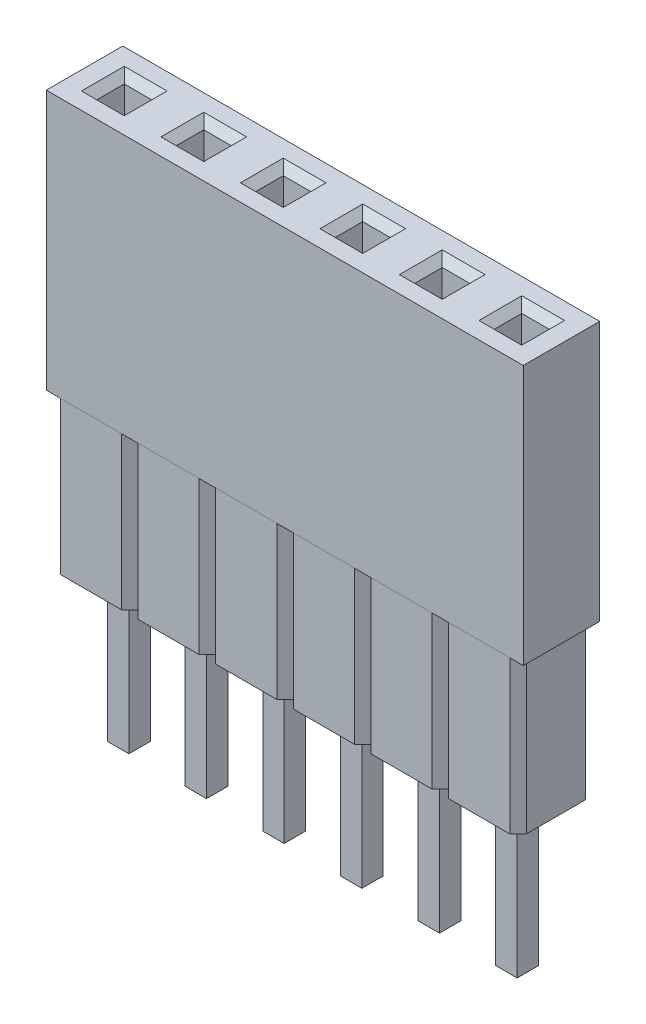
SolidWorks part; units mm, degrees
ref_plane "Alzado" through (0, 0, 0) normal (0, 0, 1) x (1, 0, 0)
ref_plane "Planta" through (0, 0, 0) normal (0, 1, 0) x (1, 0, 0)
ref_plane "Vista lateral" through (0, 0, 0) normal (1, 0, 0) x (0, 0, -1)
sketch "Croquis1" plane through (0, 0, 0) normal (0, 1, 0) x (1, 0, 0)
  line L1 (-7.8, 1.25) -> (7.8, 1.25)
  line L2 (-7.8, 1.25) -> (-7.8, -1.25)
  line L3 (-7.8, -1.25) -> (7.8, -1.25)
  line L4 (7.8, 1.25) -> (7.8, -1.25)
  line L5 (-7.8, 1.25) -> (7.8, -1.25) construction
  line L6 (-7.8, -1.25) -> (7.8, 1.25) construction
  point P0 (0, 0)
  dimension "D1" = 2.5
  dimension "D2" = 15.6
extrude "Saliente-Extruir1" add sketch "Croquis1" along normal blind 8.5
sketch "Croquis2" plane through (0, 8.5, 0) normal (0, 1, 0) x (1, 0, 0)
  line L0 (-7.8, 0) -> (7.8, 0) construction
  line L1 (-7.8, 1.25) -> (-7.8, -1.25) construction
  line L2 (7.8, -1.25) -> (7.8, 1.25) construction
  line L3 (-7.8, 1.25) -> (-5.2, 1.25) construction
  line L4 (7.8, 1.25) -> (-7.8, 1.25) construction
  line L5 (-5.2, 1.25) -> (-2.6, 1.25) construction
  line L6 (-2.6, 1.25) -> (0, 1.25) construction
  line L7 (0, 1.25) -> (2.6, 1.25) construction
  line L8 (2.6, 1.25) -> (5.2, 1.25) construction
  line L9 (-6.5, 1.25) -> (-6.5, -1.25) construction
  line L10 (-7.8, -1.25) -> (7.8, -1.25) construction
  line L11 (-3.9, 1.25) -> (-3.9, -1.25) construction
  line L12 (-1.3, 1.25) -> (-1.3, -1.25) construction
  line L13 (1.3, 1.25) -> (1.3, -1.25) construction
  line L14 (3.9, 1.25) -> (3.9, -1.25) construction
  line L15 (5.2, 1.25) -> (7.8, 1.25) construction
  line L16 (6.5, 1.25) -> (6.5, -1.25) construction
  line L18 (-7.2, 0.7) -> (-5.8, 0.7)
  line L19 (-7.2, 0.7) -> (-7.2, -0.7)
  line L20 (-7.2, -0.7) -> (-5.8, -0.7)
  line L21 (-5.8, 0.7) -> (-5.8, -0.7)
  line L22 (-7.2, 0.7) -> (-5.8, -0.7) construction
  line L23 (-7.2, -0.7) -> (-5.8, 0.7) construction
  line L24 (-4.6, 0.7) -> (-3.2, 0.7)
  line L25 (-4.6, 0.7) -> (-4.6, -0.7)
  line L26 (-4.6, -0.7) -> (-3.2, -0.7)
  line L27 (-3.2, 0.7) -> (-3.2, -0.7)
  line L28 (-4.6, 0.7) -> (-3.2, -0.7) construction
  line L29 (-4.6, -0.7) -> (-3.2, 0.7) construction
  line L30 (-2, 0.7) -> (-0.6, 0.7)
  line L31 (-2, 0.7) -> (-2, -0.7)
  line L32 (-2, -0.7) -> (-0.6, -0.7)
  line L33 (-0.6, 0.7) -> (-0.6, -0.7)
  line L34 (-2, 0.7) -> (-0.6, -0.7) construction
  line L35 (-2, -0.7) -> (-0.6, 0.7) construction
  line L36 (0.6, 0.7) -> (2, 0.7)
  line L37 (0.6, 0.7) -> (0.6, -0.7)
  line L38 (0.6, -0.7) -> (2, -0.7)
  line L39 (2, 0.7) -> (2, -0.7)
  line L40 (0.6, 0.7) -> (2, -0.7) construction
  line L41 (0.6, -0.7) -> (2, 0.7) construction
  line L42 (4.6, -0.7) -> (3.2, -0.7)
  line L43 (4.6, -0.7) -> (4.6, 0.7)
  line L44 (4.6, 0.7) -> (3.2, 0.7)
  line L45 (3.2, -0.7) -> (3.2, 0.7)
  line L46 (4.6, -0.7) -> (3.2, 0.7) construction
  line L47 (4.6, 0.7) -> (3.2, -0.7) construction
  line L48 (7.2, -0.7) -> (5.8, -0.7)
  line L49 (7.2, -0.7) -> (7.2, 0.7)
  line L50 (7.2, 0.7) -> (5.8, 0.7)
  line L51 (5.8, -0.7) -> (5.8, 0.7)
  line L52 (7.2, -0.7) -> (5.8, 0.7) construction
  line L53 (7.2, 0.7) -> (5.8, -0.7) construction
  point P31 (-6.5, 0)
  point P36 (-3.9, 0)
  point P41 (-1.3, 0)
  point P46 (1.3, 0)
  point P51 (3.9, 0)
  point P56 (6.5, 0)
  dimension "D6" = 1.4
  dimension "D1" = 2.6
  dimension "D2" = 2.6
  dimension "D3" = 2.6
  dimension "D4" = 2.6
  dimension "D5" = 2.6
  dimension "D7" = 1.4
  dimension "D8" = 1.4
  dimension "D9" = 1.4
  dimension "D10" = 1.4
  dimension "D11" = 1.4
  dimension "D12" = 1.4
  dimension "D13" = 1.4
  dimension "D14" = 1.4
  dimension "D15" = 1.4
  dimension "D16" = 1.4
  dimension "D17" = 1.4
extrude "Cortar-Extruir1" cut sketch "Croquis2" against normal blind 0.5
sketch "Croquis3" plane through (0, 8, 0) normal (0, 1, 0) x (1, 0, 0)
  line L0 (-7.2, 0) -> (7.2, 0) construction
  line L1 (-7.2, 0.7) -> (-7.2, -0.7) construction
  line L2 (7.2, -0.7) -> (7.2, 0.7) construction
  line L3 (-6.5, 0.7) -> (-6.5, -0.7) construction
  line L4 (-5.8, 0.7) -> (-7.2, 0.7) construction
  line L5 (-7.2, -0.7) -> (-5.8, -0.7) construction
  line L6 (-3.9, 0.7) -> (-3.9, -0.7) construction
  line L7 (-3.2, 0.7) -> (-4.6, 0.7) construction
  line L8 (-4.6, -0.7) -> (-3.2, -0.7) construction
  line L9 (-1.3, 0.7) -> (-1.3, -0.7) construction
  line L10 (-0.6, 0.7) -> (-2, 0.7) construction
  line L11 (-2, -0.7) -> (-0.6, -0.7) construction
  line L12 (1.3, 0.7) -> (1.3, -0.7) construction
  line L13 (2, 0.7) -> (0.6, 0.7) construction
  line L14 (0.6, -0.7) -> (2, -0.7) construction
  line L15 (3.9, 0.7) -> (3.9, -0.7) construction
  line L16 (4.6, 0.7) -> (3.2, 0.7) construction
  line L17 (3.2, -0.7) -> (4.6, -0.7) construction
  line L18 (6.5, 0.7) -> (6.5, -0.7) construction
  line L19 (7.2, 0.7) -> (5.8, 0.7) construction
  line L20 (5.8, -0.7) -> (7.2, -0.7) construction
  line L22 (-6.95, 0.45) -> (-6.05, 0.45)
  line L23 (-6.95, 0.45) -> (-6.95, -0.45)
  line L24 (-6.95, -0.45) -> (-6.05, -0.45)
  line L25 (-6.05, 0.45) -> (-6.05, -0.45)
  line L26 (-6.95, 0.45) -> (-6.05, -0.45) construction
  line L27 (-6.95, -0.45) -> (-6.05, 0.45) construction
  line L28 (-3.45, 0.45) -> (-4.35, 0.45)
  line L29 (-3.45, 0.45) -> (-3.45, -0.45)
  line L30 (-3.45, -0.45) -> (-4.35, -0.45)
  line L31 (-4.35, 0.45) -> (-4.35, -0.45)
  line L32 (-3.45, 0.45) -> (-4.35, -0.45) construction
  line L33 (-3.45, -0.45) -> (-4.35, 0.45) construction
  line L34 (-0.85, 0.45) -> (-1.75, 0.45)
  line L35 (-0.85, 0.45) -> (-0.85, -0.45)
  line L36 (-0.85, -0.45) -> (-1.75, -0.45)
  line L37 (-1.75, 0.45) -> (-1.75, -0.45)
  line L38 (-0.85, 0.45) -> (-1.75, -0.45) construction
  line L39 (-0.85, -0.45) -> (-1.75, 0.45) construction
  line L40 (0.85, 0.45) -> (1.75, 0.45)
  line L41 (0.85, 0.45) -> (0.85, -0.45)
  line L42 (0.85, -0.45) -> (1.75, -0.45)
  line L43 (1.75, 0.45) -> (1.75, -0.45)
  line L44 (0.85, 0.45) -> (1.75, -0.45) construction
  line L45 (0.85, -0.45) -> (1.75, 0.45) construction
  line L46 (3.45, 0.45) -> (4.35, 0.45)
  line L47 (3.45, 0.45) -> (3.45, -0.45)
  line L48 (3.45, -0.45) -> (4.35, -0.45)
  line L49 (4.35, 0.45) -> (4.35, -0.45)
  line L50 (3.45, 0.45) -> (4.35, -0.45) construction
  line L51 (3.45, -0.45) -> (4.35, 0.45) construction
  line L52 (6.95, -0.45) -> (6.05, -0.45)
  line L53 (6.95, -0.45) -> (6.95, 0.45)
  line L54 (6.95, 0.45) -> (6.05, 0.45)
  line L55 (6.05, -0.45) -> (6.05, 0.45)
  line L56 (6.95, -0.45) -> (6.05, 0.45) construction
  line L57 (6.95, 0.45) -> (6.05, -0.45) construction
  point P42 (-6.5, 0)
  point P47 (-3.9, 0)
  point P52 (-1.3, 0)
  point P57 (1.3, 0)
  point P62 (3.9, 0)
  point P67 (6.5, 0)
  dimension "D1" = 0.9
  dimension "D2" = 0.9
  dimension "D3" = 0.9
  dimension "D4" = 0.9
  dimension "D5" = 0.9
  dimension "D6" = 0.9
  dimension "D7" = 0.9
  dimension "D8" = 0.9
  dimension "D9" = 0.9
  dimension "D10" = 0.9
  dimension "D11" = 0.9
  dimension "D12" = 0.9
extrude "Cortar-Extruir2" cut sketch "Croquis3" against normal blind 6.5
chamfer "Chaflán1" distance 0.5 angle 45 4 edges at (-5.8, 8, 0) (-6.5, 8, -0.7) (-7.2, 8, 0) (-6.5, 8, 0.7)
chamfer "Chaflán2" distance 0.5 angle 45 4 edges at (-3.9, 8, 0.7) (-4.6, 8, 0) (-3.2, 8, 0) (-3.9, 8, -0.7)
chamfer "Chaflán3" distance 0.5 angle 45 4 edges at (-0.6, 8, 0) (-1.3, 8, -0.7) (-1.3, 8, 0.7) (-2, 8, 0)
chamfer "Chaflán4" distance 0.5 angle 45 4 edges at (1.3, 8, 0.7) (0.6, 8, 0) (2, 8, 0) (1.3, 8, -0.7)
chamfer "Chaflán5" distance 0.5 angle 45 4 edges at (3.9, 8, 0.7) (4.6, 8, 0) (3.9, 8, -0.7) (3.2, 8, 0)
chamfer "Chaflán6" distance 0.5 angle 45 4 edges at (6.5, 8, -0.7) (7.2, 8, 0) (6.5, 8, 0.7) (5.8, 8, 0)
sketch "Croquis4" plane through (0, 0, 0) normal (0, -1, 0) x (1, 0, 0)
  line L0 (-7.62, 0) -> (-5.08, 0) construction
  line L3 (-7.35, 1.24) -> (-5.35, 1.24)
  line L5 (7.62, -1.24) -> (-7.62, 1.24) construction
  line L6 (7.62, 1.24) -> (-7.62, -1.24) construction
  line L8 (-7.62, 0.97) -> (-7.35, 1.24)
  line L10 (-7.62, 0.97) -> (7.62, 0.97) construction
  line L12 (-7.62, -0.97) -> (-7.35, -1.24)
  line L14 (-7.62, -0.97) -> (7.62, -0.97) construction
  line L15 (-5.08, 0) -> (-2.54, 0) construction
  line L16 (-2.54, 0) -> (0, 0) construction
  line L17 (0, 0) -> (2.54, 0) construction
  line L18 (2.54, 0) -> (5.08, 0) construction
  line L19 (5.08, 0) -> (7.62, 0) construction
  line L20 (-5.08, 0) -> (-5.08, -1.24) construction
  line L21 (-2.54, 0) -> (-2.54, -1.24) construction
  line L22 (0, 0) -> (0, -1.24) construction
  line L23 (2.54, 0) -> (2.54, -1.24) construction
  line L24 (5.08, 0) -> (5.08, -1.24) construction
  line L26 (-5.35, -1.24) -> (-5.08, -0.97)
  line L27 (-5.08, -0.97) -> (-4.81, -1.24)
  line L31 (-2.81, -1.24) -> (-2.54, -0.97)
  line L32 (-2.54, -0.97) -> (-2.27, -1.24)
  line L35 (0.27, -1.24) -> (0, -0.97)
  line L36 (0, -0.97) -> (-0.27, -1.24)
  line L39 (2.81, -1.24) -> (2.54, -0.97)
  line L40 (2.54, -0.97) -> (2.27, -1.24)
  line L43 (5.35, -1.24) -> (5.08, -0.97)
  line L44 (5.08, -0.97) -> (4.81, -1.24)
  line L46 (7.62, -0.97) -> (7.35, -1.24)
  line L50 (7.35, 1.24) -> (7.62, 0.97)
  line L52 (5.35, 1.24) -> (5.08, 0.97)
  line L53 (5.08, 0.97) -> (4.81, 1.24)
  line L56 (2.81, 1.24) -> (2.54, 0.97)
  line L57 (2.54, 0.97) -> (2.27, 1.24)
  line L59 (0, 0.97) -> (0.27, 1.24)
  line L62 (-0.27, 1.24) -> (0, 0.97)
  line L64 (-2.27, 1.24) -> (-2.54, 0.97)
  line L65 (-2.54, 0.97) -> (-2.81, 1.24)
  line L68 (-4.81, 1.24) -> (-5.08, 0.97)
  line L69 (-5.08, 0.97) -> (-5.35, 1.24)
  line L71 (-4.81, 1.24) -> (-2.81, 1.24)
  line L73 (-2.27, 1.24) -> (-0.27, 1.24)
  line L74 (0.27, 1.24) -> (2.27, 1.24)
  line L75 (2.81, 1.24) -> (4.81, 1.24)
  line L77 (5.35, 1.24) -> (7.35, 1.24)
  line L78 (7.62, 0.97) -> (7.62, -0.97)
  line L79 (7.35, -1.24) -> (5.35, -1.24)
  line L80 (4.81, -1.24) -> (2.81, -1.24)
  line L81 (2.27, -1.24) -> (0.27, -1.24)
  line L82 (-0.27, -1.24) -> (-2.27, -1.24)
  line L83 (-2.81, -1.24) -> (-4.81, -1.24)
  line L84 (-5.35, -1.24) -> (-7.35, -1.24)
  line L85 (-7.62, -0.97) -> (-7.62, 0.97)
  point P0 (0, 0)
  dimension "D23" = 0.27
  dimension "D1" = 15.24
  dimension "D2" = 2.48
  dimension "D3" = 0.27
  dimension "D4" = 0.27
  dimension "D5" = 0.27
  dimension "D6" = 0.27
  dimension "D7" = 2.54
  dimension "D8" = 2.54
  dimension "D9" = 2.54
  dimension "D10" = 2.54
  dimension "D11" = 2.54
  dimension "D12" = 2.54
  dimension "D13" = 0.27
  dimension "D14" = 0.27
  dimension "D15" = 0.27
  dimension "D16" = 0.27
  dimension "D17" = 0.27
  dimension "D18" = 0.27
  dimension "D19" = 0.27
  dimension "D20" = 0.27
  dimension "D21" = 0.27
  dimension "D22" = 0.27
  dimension "D24" = 0.27
  dimension "D25" = 0.54
  dimension "D26" = 0.54
  dimension "D31" = 0.54
extrude "Saliente-Extruir2" add sketch "Croquis4" along normal blind 5
sketch "Croquis5" plane through (0, -5, 0) normal (0, -1, 0) x (1, 0, 0)
  line L0 (-7.62, 0) -> (7.62, 0) construction
  line L1 (-7.62, 0.97) -> (-7.62, -0.97) construction
  line L2 (7.62, -0.97) -> (7.62, 0.97) construction
  line L3 (-6.35, 1.24) -> (-6.35, -1.24) construction
  line L4 (-5.35, 1.24) -> (-7.35, 1.24) construction
  line L5 (-7.35, -1.24) -> (-5.35, -1.24) construction
  line L6 (-3.81, 1.24) -> (-3.81, -1.24) construction
  line L7 (-2.81, 1.24) -> (-4.81, 1.24) construction
  line L8 (-4.81, -1.24) -> (-2.81, -1.24) construction
  line L9 (-1.27, 1.24) -> (-1.27, -1.24) construction
  line L10 (-0.27, 1.24) -> (-2.27, 1.24) construction
  line L11 (-2.27, -1.24) -> (-0.27, -1.24) construction
  line L12 (1.27, 1.24) -> (1.27, -1.24) construction
  line L13 (2.27, 1.24) -> (0.27, 1.24) construction
  line L14 (0.27, -1.24) -> (2.27, -1.24) construction
  line L15 (3.81, 1.24) -> (3.81, -1.24) construction
  line L16 (4.81, 1.24) -> (2.81, 1.24) construction
  line L17 (2.81, -1.24) -> (4.81, -1.24) construction
  line L18 (6.35, 1.24) -> (6.35, -1.24) construction
  line L19 (7.35, 1.24) -> (5.35, 1.24) construction
  line L20 (5.35, -1.24) -> (7.35, -1.24) construction
  line L22 (-6.7, 0.35) -> (-6, 0.35)
  line L23 (-6.7, 0.35) -> (-6.7, -0.35)
  line L24 (-6.7, -0.35) -> (-6, -0.35)
  line L25 (-6, 0.35) -> (-6, -0.35)
  line L26 (-6.7, 0.35) -> (-6, -0.35) construction
  line L27 (-6.7, -0.35) -> (-6, 0.35) construction
  line L28 (-3.46, -0.35) -> (-4.16, -0.35)
  line L29 (-3.46, -0.35) -> (-3.46, 0.35)
  line L30 (-3.46, 0.35) -> (-4.16, 0.35)
  line L31 (-4.16, -0.35) -> (-4.16, 0.35)
  line L32 (-3.46, -0.35) -> (-4.16, 0.35) construction
  line L33 (-3.46, 0.35) -> (-4.16, -0.35) construction
  line L34 (-0.92, -0.35) -> (-1.62, -0.35)
  line L35 (-0.92, -0.35) -> (-0.92, 0.35)
  line L36 (-0.92, 0.35) -> (-1.62, 0.35)
  line L37 (-1.62, -0.35) -> (-1.62, 0.35)
  line L38 (-0.92, -0.35) -> (-1.62, 0.35) construction
  line L39 (-0.92, 0.35) -> (-1.62, -0.35) construction
  line L40 (1.62, -0.35) -> (0.92, -0.35)
  line L41 (1.62, -0.35) -> (1.62, 0.35)
  line L42 (1.62, 0.35) -> (0.92, 0.35)
  line L43 (0.92, -0.35) -> (0.92, 0.35)
  line L44 (1.62, -0.35) -> (0.92, 0.35) construction
  line L45 (1.62, 0.35) -> (0.92, -0.35) construction
  line L46 (4.16, -0.35) -> (3.46, -0.35)
  line L47 (4.16, -0.35) -> (4.16, 0.35)
  line L48 (4.16, 0.35) -> (3.46, 0.35)
  line L49 (3.46, -0.35) -> (3.46, 0.35)
  line L50 (4.16, -0.35) -> (3.46, 0.35) construction
  line L51 (4.16, 0.35) -> (3.46, -0.35) construction
  line L52 (6.7, -0.35) -> (6, -0.35)
  line L53 (6.7, -0.35) -> (6.7, 0.35)
  line L54 (6.7, 0.35) -> (6, 0.35)
  line L55 (6, -0.35) -> (6, 0.35)
  line L56 (6.7, -0.35) -> (6, 0.35) construction
  line L57 (6.7, 0.35) -> (6, -0.35) construction
  point P42 (-6.35, 0)
  point P47 (-3.81, 0)
  point P52 (-1.27, 0)
  point P57 (1.27, 0)
  point P62 (3.81, 0)
  point P67 (6.35, 0)
  dimension "D1" = 0.7
  dimension "D2" = 0.7
  dimension "D3" = 0.7
  dimension "D4" = 0.7
  dimension "D5" = 0.7
  dimension "D6" = 0.7
  dimension "D7" = 0.7
  dimension "D8" = 0.7
  dimension "D9" = 0.7
  dimension "D10" = 0.7
  dimension "D11" = 0.7
  dimension "D12" = 0.7
extrude "Saliente-Extruir3" add sketch "Croquis5" along normal blind 4.85
